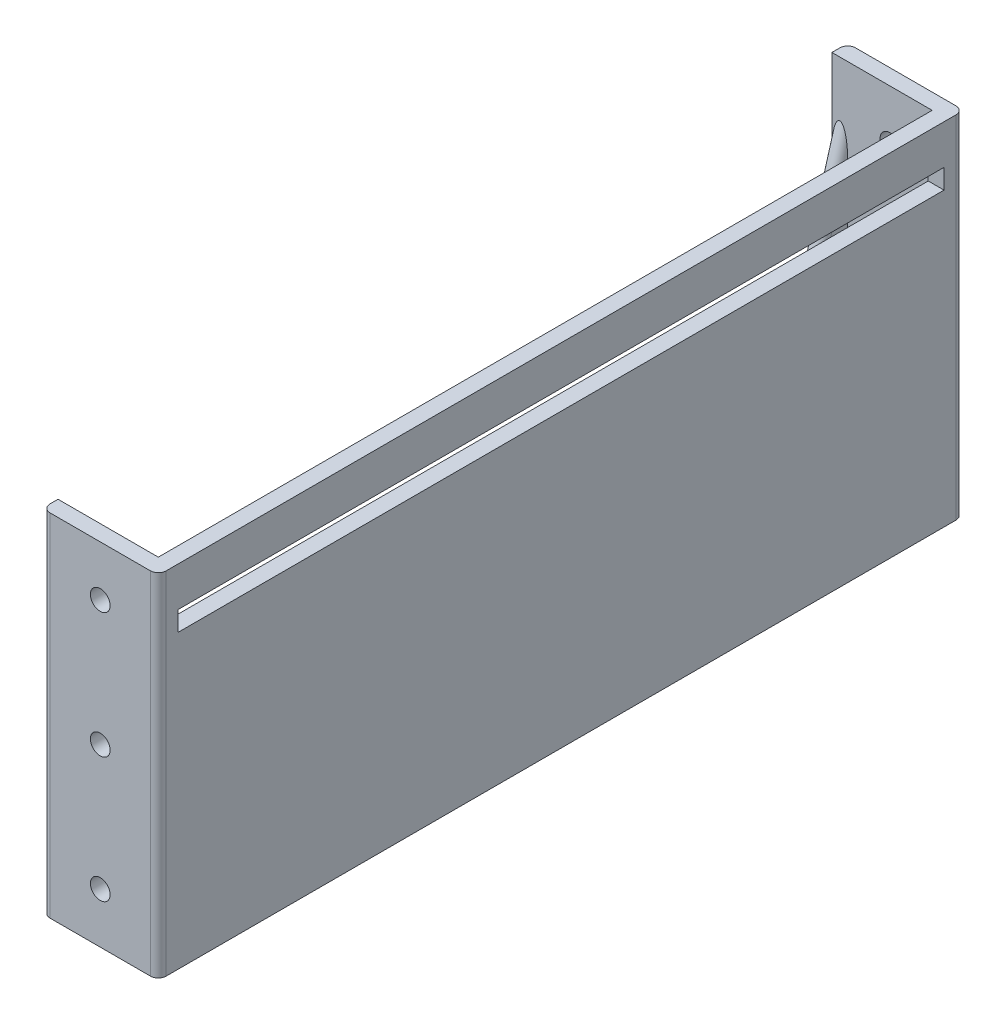
SolidWorks part; units mm, degrees
ref_plane "Front Plane" through (0, 0, 0) normal (0, 0, 1) x (1, 0, 0)
ref_plane "Top Plane" through (0, 0, 0) normal (0, 1, 0) x (1, 0, 0)
ref_plane "Right Plane" through (0, 0, 0) normal (1, 0, 0) x (0, 0, -1)
sketch "Sketch1" plane through (0, 0, 0) normal (0, 0, 1) x (1, 0, 0)
  line L1 (0, 0) -> (25.4, 0)
  line L2 (0, 0) -> (0, 88.9)
  line L3 (0, 88.9) -> (25.4, 88.9)
  line L4 (25.4, 0) -> (25.4, 88.9)
  dimension "D1" = 88.9
  dimension "D2" = 25.4
extrude "Boss-Extrude1" add sketch "Sketch1" along normal blind 4
sketch "Sketch2" plane through (25.4, 0, 0) normal (1, 0, 0) x (0, 0, -1)
  line L0 (-4, 88.9) -> (0, 88.9) construction
  line L1 (-4, 0) -> (196, 0)
  line L2 (-4, 0) -> (-4, 88.9)
  line L3 (-4, 88.9) -> (196, 88.9)
  line L4 (196, 0) -> (196, 88.9)
  dimension "D1" = 200
extrude "Boss-Extrude2" add sketch "Sketch2" along normal blind 4
sketch "Sketch3" plane through (0, 0, -196) normal (0, 0, -1) x (-1, 0, 0)
  line L0 (0, 88.9) -> (0, 0) construction
  line L1 (-29.4, 0) -> (0, 0)
  line L2 (-29.4, 0) -> (-29.4, 88.9)
  line L3 (-29.4, 88.9) -> (0, 88.9)
  line L4 (0, 0) -> (0, 88.9)
  line L5 (-25.4, 88.9) -> (0, 88.9) construction
extrude "Boss-Extrude3" add sketch "Sketch3" along normal blind 4
sketch "Sketch4" plane through (0, 0, 0) normal (0, -1, 0) x (-1, 0, 0)
  line L1 (-29.4, 200) -> (0, 200)
  line L2 (-29.4, 200) -> (-29.4, -4)
  line L3 (-29.4, -4) -> (0, -4)
  line L4 (0, 200) -> (0, -4)
extrude "Boss-Extrude4" add sketch "Sketch4" against normal blind 4
sketch "Sketch5" plane through (0, 0, 0) normal (-1, 0, 0) x (0, 0, 1)
  line L0 (-200, 88.9) -> (-200, 0)
  line L2 (-200, 0) -> (-174.6, 0)
  line L3 (4, 0) -> (-200, 0) construction
  line L4 (-174.6, 0) -> (-200, 88.9)
  line L5 (4, 0) -> (-21.4, 0)
  line L6 (-21.4, 0) -> (4, 88.9)
  line L7 (4, 88.9) -> (4, 0) construction
  line L8 (4, 88.9) -> (4, 0)
  point P2 (-200, 88.9)
  point P3 (4, 88.9)
  point P11 (0, 0)
  point P15 (4, 88.9)
  dimension "D2" = 25.4
  dimension "D3" = 25.4
extrude "Boss-Extrude5" add sketch "Sketch5" against normal blind 4
sketch "Sketch6" plane through (0, 0, -200) normal (0, 0, -1) x (-1, 0, 0)
  line L0 (-14.7, 88.9) -> (-14.7, 0) construction
  line L1 (0, 88.9) -> (-29.4, 88.9) construction
  line L2 (-29.4, 0) -> (0, 0) construction
  circle A0 centre (-14.7, 12.75) radius 2.5
  circle A1 centre (-14.7, 76.15) radius 2.5
  circle A2 centre (-14.7, 44.45) radius 2.5
  dimension "D1" = 5
  dimension "D2" = 12.75
  dimension "D3" = 12.75
extrude "Cut-Extrude1" cut sketch "Sketch6" against normal through all
fillet "Fillet1" 2 edges at (0, 39.45, -185.8714) (4, 39.45, -185.8714) type full round first side face at (0, 51.34, -98) second side face at (4, 27.6333, -189.2476) middle face at (2, 39.45, -185.8714)
fillet "Fillet2" 2 edges at (0, 39.45, -10.1286) (4, 39.45, -10.1286) type full round first side face at (0, 50.612, -98.208) second side face at (4, 27.6333, -6.7524) middle face at (2, 39.45, -10.1286)
fillet "Fillet3" radius 2 4 edges at (0, 44.45, 4) (29.4, 44.45, 4) (29.4, 44.45, -200) (0, 44.45, -200)
sketch "Sketch7" plane through (29.4, 0, 0) normal (1, 0, 0) x (0, 0, -1)
  line L0 (198, 88.9) -> (-2, 88.9) construction
  line L1 (1, 78.9) -> (195, 78.9)
  line L2 (1, 78.9) -> (1, 73.9)
  line L3 (1, 73.9) -> (195, 73.9)
  line L4 (195, 78.9) -> (195, 73.9)
  line L5 (-4, 0) -> (-4, 88.9) construction
  line L6 (200, 88.9) -> (200, 0) construction
  dimension "D1" = 10
  dimension "D2" = 5
  dimension "D3" = 5
  dimension "D4" = 5
extrude "Cut-Extrude2" cut sketch "Sketch7" against normal blind 4
